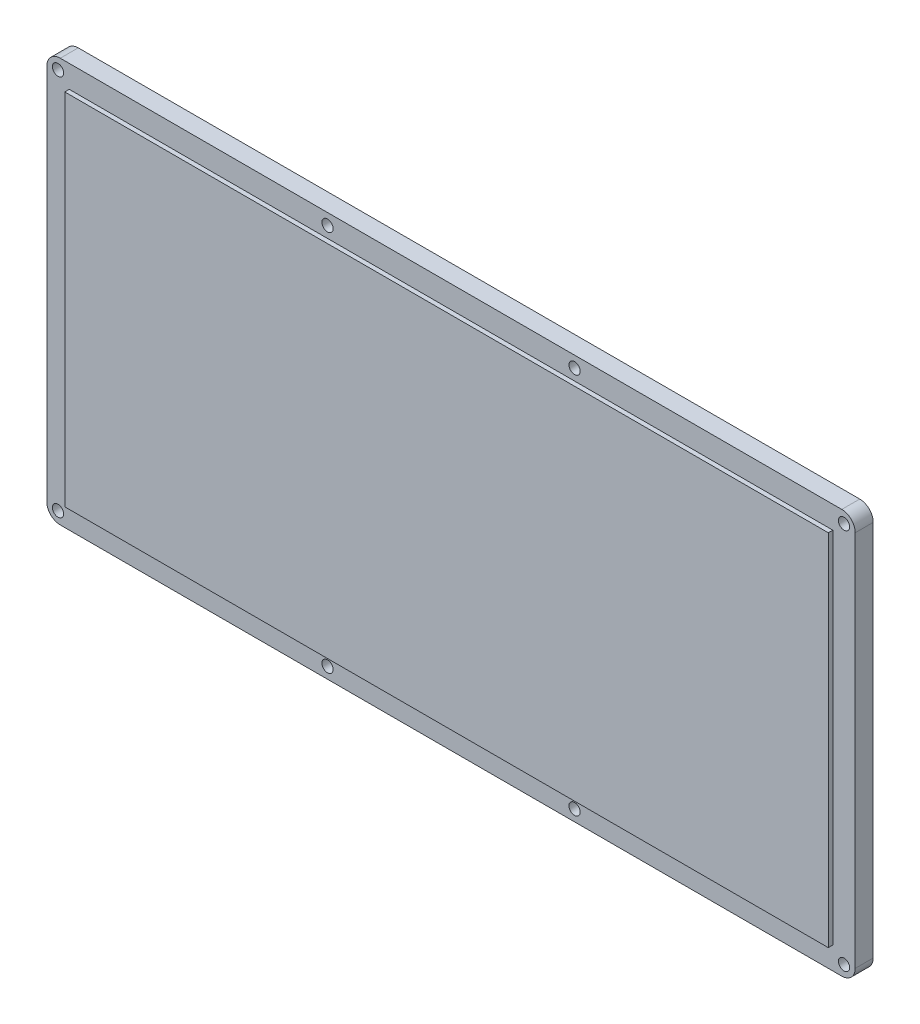
SolidWorks part; units mm, degrees
ref_plane "Front Plane" through (0, 0, 0) normal (0, 0, 1) x (1, 0, 0)
ref_plane "Top Plane" through (0, 0, 0) normal (0, 1, 0) x (1, 0, 0)
ref_plane "Right Plane" through (0, 0, 0) normal (1, 0, 0) x (0, 0, -1)
sketch "Sketch1" plane through (0, 0, 0) normal (0, 0, 1) x (1, 0, 0)
  line L1 (-90, 45) -> (90, 45)
  line L2 (-90, 45) -> (-90, -45)
  line L3 (-90, -45) -> (90, -45)
  line L4 (90, 45) -> (90, -45)
  point P4 (0, 45)
  point P6 (-90, 0)
  dimension "D1" = 180
  dimension "D2" = 90
extrude "Boss-Extrude1" add sketch "Sketch1" along normal blind 4
fillet "Fillet1" radius 3 4 edges at (90, 45, 2) (90, -45, 2) (-90, -45, 2) (-90, 45, 2)
sketch "Sketch2" plane through (0, 0, 4) normal (0, 0, 1) x (1, 0, 0)
  line L8 (85, -40) -> (85, 40)
  line L9 (85, 40) -> (-85, 40)
  line L10 (-85, 40) -> (-85, -40)
  line L11 (-85, -40) -> (85, -40)
  line L12 (85, -40) -> (85, 40)
  line L13 (85, 40) -> (-85, 40)
  line L14 (-85, 40) -> (-85, -40)
  line L15 (-85, -40) -> (85, -40)
  dimension "D1" = 5
extrude "Boss-Extrude2" add sketch "Sketch2" along normal blind 1
sketch "Sketch3" plane through (0, 0, 0) normal (0, 0, -1) x (-1, 0, 0)
  line L1 (-87.5, 42.5) -> (87.5, 42.5) construction
  line L2 (-87.5, 42.5) -> (-87.5, -42.5) construction
  line L3 (-87.5, -42.5) -> (87.5, -42.5) construction
  line L4 (87.5, 42.5) -> (87.5, -42.5) construction
  line L5 (-90, -42) -> (-90, 42) construction
  line L6 (-87, 45) -> (87, 45) construction
  circle A0 centre (-87.5, 42.5) radius 1.25
  circle A1 centre (87.5, 42.5) radius 1.25
  circle A2 centre (87.5, -42.5) radius 1.25
  circle A3 centre (-87.5, -42.5) radius 1.25
  circle A4 centre (-27.5, -42.5) radius 1.25
  circle A5 centre (27.5, 42.5) radius 1.25
  circle A6 centre (27.5, -42.5) radius 1.25
  circle A7 centre (-27.5, 42.5) radius 1.25
  point P4 (0, 42.5)
  point P6 (-87.5, 0)
  dimension "D1" = 2.5
  dimension "D4" = 2.5
  dimension "D5" = 2.5
  dimension "D6" = 60
  dimension "D7" = 2.5
  dimension "D8" = 60
  dimension "D9" = 60
  dimension "D10" = 2.5
  dimension "D2" = 2.5
  dimension "D3" = 2.5
  dimension "D11" = 60
extrude "Cut-Extrude2" cut sketch "Sketch3" against normal blind 10
sketch "Sketch4" plane through (0, 0, 0) normal (0, 0, -1) x (-1, 0, 0)
  text T0 "OSCC" font "Century Gothic" height in points 72
extrude "Boss-Extrude3" add sketch "Sketch4" along normal blind 0.5
sketch "Sketch5" plane through (0, 0, 0) normal (0, 0, -1) x (-1, 0, 0)
  line L0 (-46.627, 30.9335) -> (-64.3183, 20.6698)
  line L1 (-64.3183, 20.6698) -> (-46.627, 10.5547)
  line L2 (-46.627, 10.5547) -> (-46.627, 30.9335)
  line L3 (-72.1621, 20.6698) -> (-42.8333, 37.6851)
  line L4 (-42.8333, 37.6851) -> (-42.8333, 3.9008)
  line L5 (-42.8333, 3.9008) -> (-72.1621, 20.6698)
  line L6 (-72.2687, -19.4106) -> (-42.8868, -2.4872)
  line L7 (-42.8868, -2.4872) -> (-42.8868, -36.2716)
  line L8 (-42.8868, -36.2716) -> (-72.2687, -19.4106)
  line L9 (-37.4108, 0.6761) -> (-8.0819, 17.6916)
  line L10 (-8.0819, 17.6916) -> (-8.0819, -16.0927)
  line L11 (-8.0819, -16.0927) -> (-37.4108, 0.6761)
  line L12 (-39.2453, -2.5012) -> (-9.9162, -19.2701)
  line L13 (-9.9162, -19.2701) -> (-39.2453, -36.2855)
  line L14 (-39.2453, -36.2855) -> (-39.2453, -2.5012)
  line L15 (-73.793, 17.5357) -> (-44.3574, 0.7057)
  line L16 (-44.3574, 0.7057) -> (-73.793, -16.2486)
  line L17 (-73.793, -16.2486) -> (-73.793, 17.5357)
  line L18 (-39.2356, 37.1003) -> (-9.9066, 20.2697)
  line L19 (-9.9066, 20.2697) -> (-39.2356, 3.2542)
  line L20 (-39.2356, 3.2542) -> (-39.2356, 37.1003)
extrude "Boss-Extrude4" add sketch "Sketch5" along normal blind 0.5
